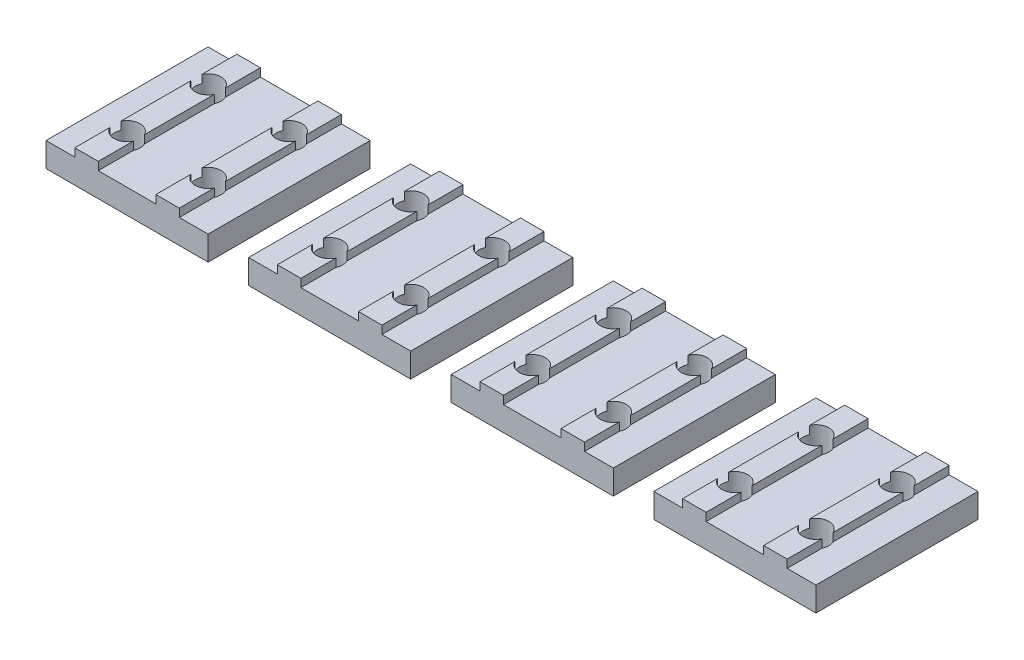
SolidWorks part; units mm, degrees
ref_plane "Front Plane" through (0, 0, 0) normal (0, 0, 1) x (1, 0, 0)
ref_plane "Top Plane" through (0, 0, 0) normal (0, 1, 0) x (1, 0, 0)
ref_plane "Right Plane" through (0, 0, 0) normal (1, 0, 0) x (0, 0, -1)
sketch "Esquisse1" plane through (0, 0, 0) normal (0, 0, 1) x (1, 0, 0)
  line L0 (-5, 0) -> (-5, 3)
  line L1 (-5, 3) -> (-1.45, 3)
  line L2 (-1.45, 3) -> (-1.45, 4)
  line L3 (-1.45, 4) -> (1.45, 4)
  line L4 (1.45, 4) -> (1.45, 3)
  line L5 (1.45, 3) -> (5, 3)
  line L6 (5, 3) -> (5, 0)
  line L7 (5, 0) -> (-5, 0)
  point P7 (0, 0)
  point P11 (0, 0)
  dimension "D1" = 10
  dimension "D2" = 3
  dimension "D3" = 1
  dimension "D4" = 2.9
  dimension "D5" = 3.55
extrude "Main" add sketch "Esquisse1" along normal blind 20
sketch "Esquisse2" plane through (0, 4, 0) normal (0, 1, 0) x (1, 0, 0)
  line L0 (0, -2.2) -> (0, 2.2) construction
  line L1 (-1.45, 0) -> (-5, 0) construction
  line L2 (-1.45, -20) -> (-5, -20) construction
  circle A0 centre (0, -5) radius 1.6
  circle A1 centre (0, -15) radius 1.6
  point P4 (0, 0)
  point P5 (0, -2.3892)
  point P6 (0, -16.6698)
  point P7 (0, 0)
  point P10 (0, -2.5276)
  point P11 (0, -16.7528)
  dimension "D2" = 5
  dimension "D3" = 3.2
  dimension "D1" = 5
extrude "TopHole" cut sketch "Esquisse2" against normal through all
ref_axis "Axe1" through (-5.5, 0, 0) along (1, 0, 0)
pattern_linear "Répétition linéaire1" count 2 spacing 10 along (-1, 0, 0) of "TopHole", "Main"
pattern_linear "Répétition linéaire2" count 4 spacing 25 along (-1, 0, 0) of "Répétition linéaire1"
